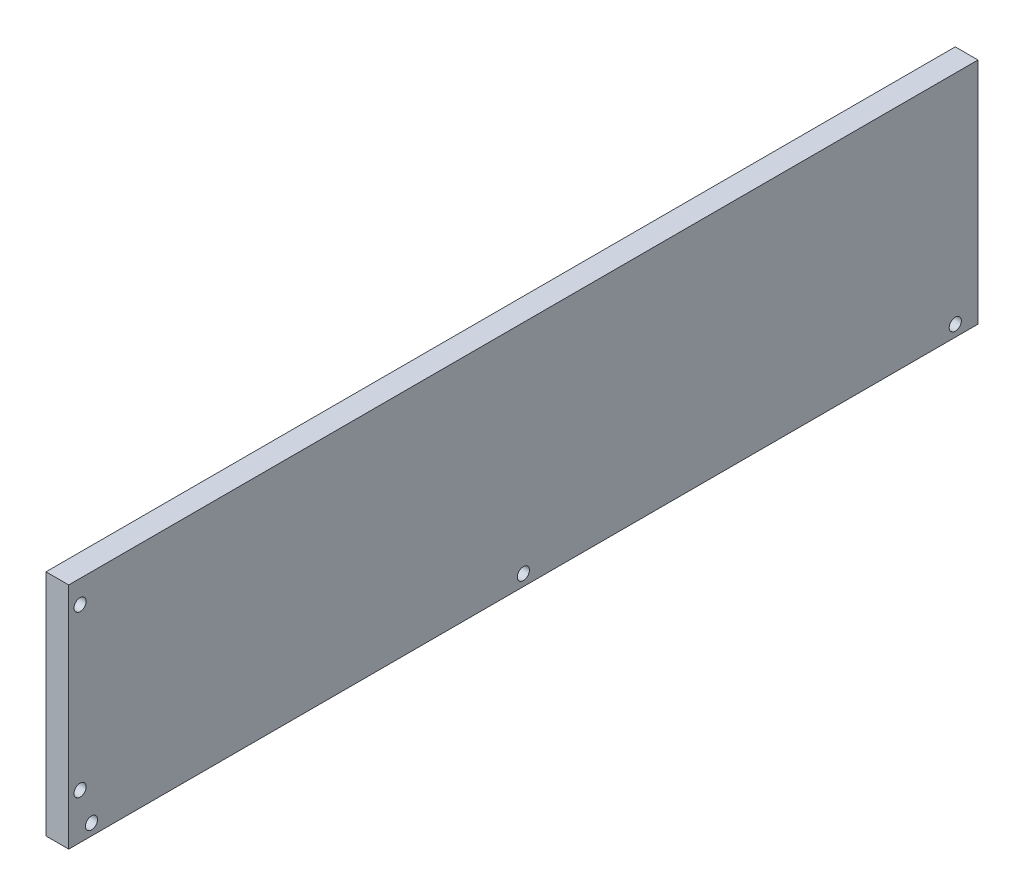
SolidWorks part; units mm, degrees
material "Oak"
ref_plane "Front Plane" through (0, 0, 0) normal (0, 0, 1) x (1, 0, 0)
ref_plane "Top Plane" through (0, 0, 0) normal (0, 1, 0) x (1, 0, 0)
ref_plane "Right Plane" through (0, 0, 0) normal (1, 0, 0) x (0, 0, -1)
sketch "Sketch1" plane through (0, 0, 0) normal (1, 0, 0) x (0, 0, -1)
  line L1 (-300, -75.5) -> (300, -75.5)
  line L2 (-300, -75.5) -> (-300, 75.5)
  line L3 (-300, 75.5) -> (300, 75.5)
  line L4 (300, -75.5) -> (300, 75.5)
  line L5 (-300, -75.5) -> (300, 75.5) construction
  line L6 (-300, 75.5) -> (300, -75.5) construction
  point P0 (0, 0)
  dimension "D1" = 600
  dimension "D2" = 151
extrude "Boss-Extrude1" add sketch "Sketch1" along normal blind 15
sketch "Sketch2" plane through (15, 0, 0) normal (1, 0, 0) x (0, 0, -1)
  line L0 (-300, -60.5) -> (300, -60.5) construction
  line L1 (-300, 75.5) -> (-300, -75.5) construction
  line L2 (300, -75.5) -> (300, 75.5) construction
  line L3 (-300, -75.5) -> (300, -75.5) construction
  line L4 (-285, -60.5) -> (-285, -75.5) construction
  line L5 (300, -68) -> (289, -68) construction
  line L6 (300, -60.5) -> (300, -75.5) construction
  line L7 (-285, 75.5) -> (-285, -60.5) construction
  line L8 (300, 75.5) -> (-300, 75.5) construction
  line L9 (-285, -45.5) -> (-300, -45.5) construction
  line L10 (-285, 75.5) -> (-300, 75.5) construction
  line L11 (-292.5, 75.5) -> (-292.5, 64.5) construction
  circle A0 centre (285, -68) radius 4
  circle A1 centre (-292.5, 60.5) radius 4
  dimension "D1" = 15
  dimension "D4" = 8
  dimension "D2" = 15
  dimension "D3" = 11
  dimension "D5" = 15
  dimension "D6" = 15
  dimension "D8" = 11
extrude "Cut-Extrude1" cut sketch "Sketch2" against normal blind 10 contours A0 region at (15, -68, -285)
extrude "Cut-Extrude2" cut sketch "Sketch2<3>" against normal blind 10 contours A1 region at (15, 60.5, 292.5)
sketch "Sketch2<3>" plane through (15, 0, 0) normal (1, 0, 0) x (0, 0, -1) same geometry as "Sketch2"
pattern_linear "LPattern1" count 3 spacing 285 along (0, 0, 1) of "Cut-Extrude1"
pattern_linear "LPattern2" count 2 spacing 106 along (0, -1, 0) of "Cut-Extrude2"
sketch "Sketch3" [suppressed] plane through (14, 0, 0) normal (1, 0, 0) x (0, 0, -1)
  line L0 (300, -61.5) -> (-300, -61.5) construction
  line L1 (300, -75.5) -> (300, 75.5) construction
  line L2 (-300, 75.5) -> (-300, -75.5) construction
  line L3 (286, 75.5) -> (286, -61.5) construction
  line L4 (300, 75.5) -> (-300, 75.5) construction
  line L5 (286, -46.5) -> (300, -46.5) construction
  line L6 (293, 75.5) -> (293, 64.5) construction
  line L7 (-300, -75.5) -> (300, -75.5) construction
  line L8 (286, 75.5) -> (300, 75.5) construction
  circle A0 centre (293, 60.5) radius 4
  point P21 (293, 75.5)
  dimension "D1" = 15
  dimension "D2" = 15
  dimension "D5" = 15
  dimension "D3" = 8
  dimension "D4" = 11
extrude "Cut-Extrude3" [suppressed] cut sketch "Sketch3" against normal blind 10
pattern_linear "LPattern3" [suppressed] count 2 spacing 107 of bodies 106
sketch "Sketch4" [suppressed] plane through (0, 0, 300) normal (0, 0, 1) x (1, 0, 0)
  line L0 (0, -60.5) -> (14, -60.5) construction
  line L1 (0, 75.5) -> (0, -75.5) construction
  line L2 (14, 75.5) -> (14, -75.5) construction
  line L3 (7, 75.5) -> (7, 64.5) construction
  line L4 (14, 75.5) -> (0, 75.5) construction
  line L5 (14, -75.5) -> (0, -75.5) construction
  circle A0 centre (7, 60.5) radius 4
  dimension "D1" = 8
  dimension "D2" = 11
  dimension "D3" = 15
extrude "Cut-Extrude4" [suppressed] cut sketch "Sketch4" against normal blind 10
pattern_linear "LPattern4" [suppressed] count 2 spacing 121 of bodies 108
sketch "Sketch5" plane through (0, 0, -300) normal (0, 0, -1) x (-1, 0, 0)
  line L0 (-15, -60.5) -> (0, -60.5) construction
  line L1 (-15, -75.5) -> (-15, 75.5) construction
  line L2 (0, -75.5) -> (0, 75.5) construction
  line L3 (-7.5, 75.5) -> (-7.5, 64.5) construction
  line L4 (-15, 75.5) -> (0, 75.5) construction
  line L5 (-15, -75.5) -> (0, -75.5) construction
  circle A0 centre (-7.5, 60.5) radius 4
  dimension "D1" = 8
  dimension "D2" = 11
  dimension "D3" = 15
extrude "Cut-Extrude5" cut sketch "Sketch5" against normal blind 10
pattern_linear "LPattern5" count 2 spacing 121 along (0, -1, 0) of "Cut-Extrude5"
equation "\"A\"= 600mm"
equation "\"B\"= 151mm"
equation "\"C\"= 15mm"
equation "\"D1@Sketch1\"=\"A\""
equation "\"D2@Sketch1\"=\"B\""
equation "\"D1@Boss-Extrude1\"=\"C\""
equation "\"D1@Sketch2\"=\"C\""
equation "\"D5@Sketch2\"=\"C\""
equation "\"D1@Sketch3\"=\"C\""
equation "\"D2@Sketch3\"=\"C\""
